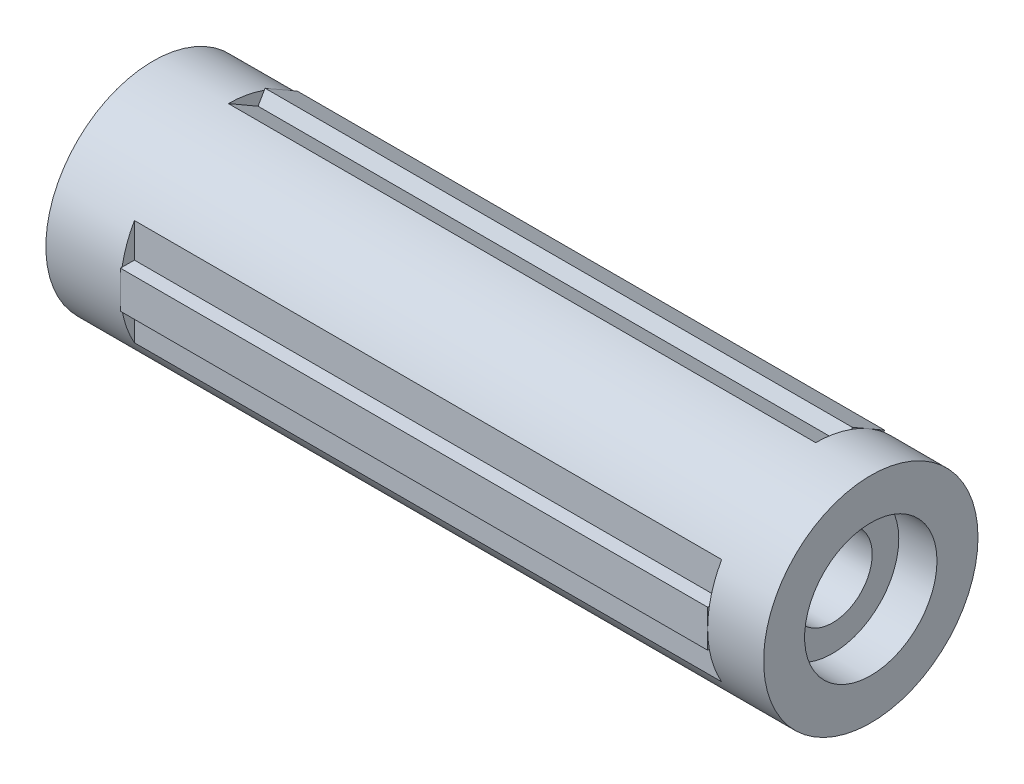
SolidWorks part; units mm, degrees
material "PVC hart"
ref_plane "Ebene vorne" through (0, 0, 0) normal (0, 0, 1) x (1, 0, 0)
ref_plane "Ebene oben" through (0, 0, 0) normal (0, 1, 0) x (1, 0, 0)
ref_plane "Ebene rechts" through (0, 0, 0) normal (1, 0, 0) x (0, 0, -1)
sketch "Skizze1" plane through (0, 0, 0) normal (1, 0, 0) x (0, 0, -1)
  circle A0 centre (0, 0) radius 11.5
  dimension "D1" = 23
extrude "Aufsatz-Linear austragen1" add sketch "Skizze1" along normal blind 77
sketch "Skizze2" plane through (77, 0, 0) normal (1, 0, 0) x (0, 0, -1)
  circle A0 centre (0, 0) radius 7.1
  dimension "D1" = 14.2
extrude "Schnitt-Linear austragen1" cut sketch "Skizze2" against normal blind 4.1
sketch "Skizze3" plane through (72.9, 0, 0) normal (1, 0, 0) x (0, 0, -1)
  circle A0 centre (0, 0) radius 4.25
  dimension "D1" = 8.5
extrude "Schnitt-Linear austragen2" cut sketch "Skizze3" against normal blind 11
sketch "Skizze4" plane through (0, 0, 0) normal (-1, 0, 0) x (0, 0, 1)
  circle A0 centre (0, 0) radius 9.6
  dimension "D1" = 19.2
extrude "Schnitt-Linear austragen3" cut sketch "Skizze4" against normal blind 12.75
sketch "Skizze7" plane through (77, 0, 0) normal (1, 0, 0) x (0, 0, -1)
  line L0 (0, 13.4409) -> (0, -14.2481) construction
  line L1 (-11.5, 7.5) -> (-10, 7.5)
  line L2 (-11.5, 7.5) -> (-11.5, -7.5)
  line L3 (-11.5, -7.5) -> (-10, -7.5)
  line L4 (-10, 7.5) -> (-10, -7.5)
  dimension "D1" = 1.5
  dimension "D2" = 15
  dimension "D3" = 10
extrude "Schnitt-Linear austragen4" cut sketch "Skizze7" against normal blind 63 from offset 6 offset against normal yes
sketch "Skizze8" plane through (0, 0, 10) normal (0, 0, 1) x (1, 0, 0)
  line L0 (71, -5.6789) -> (71, 5.6789) construction
  line L1 (8, 2) -> (71, 2)
  line L2 (8, 2) -> (8, -2)
  line L3 (8, -2) -> (71, -2)
  line L4 (71, 2) -> (71, -2)
  line L5 (8, 2) -> (71, -2) construction
  line L6 (8, -2) -> (71, 2) construction
  line L7 (12.65, 0) -> (-12.65, 0) construction
  point P0 (39.5, 0)
  dimension "D1" = 31.5
  dimension "D3" = 63
  dimension "D4" = 4
extrude "Aufsatz-Linear austragen2" add sketch "Skizze8" along normal blind 1.5
sketch "Skizze10" plane through (12.75, 0, 0) normal (-1, 0, 0) x (0, 0, 1)
  line L1 (4.0389, -2.2407) -> (3.96, 2.3774)
  line L2 (3.96, 2.3774) -> (-0.0789, 4.6181)
  line L3 (-0.0789, 4.6181) -> (-4.0389, 2.2407)
  line L4 (-4.0389, 2.2407) -> (-3.96, -2.3774)
  line L5 (-3.96, -2.3774) -> (0.0789, -4.6181)
  line L6 (0.0789, -4.6181) -> (4.0389, -2.2407)
  circle A0 centre (0, 0) radius 4 construction
  dimension "D1" = 8
extrude "Schnitt-Linear austragen6" cut sketch "Skizze10" against normal blind 13.5
sketch "Skizze12" plane through (26.25, 0, 0) normal (-1, 0, 0) x (0, 0, 1)
  circle A0 centre (0, 0) radius 3
  dimension "D1" = 6
extrude "Schnitt-Linear austragen7" cut sketch "Skizze12" against normal blind 2
pattern_circular "Kreismuster3" count 3 over 360 about axis through (77, 0, 0) along (-1, 0, 0) of "Aufsatz-Linear austragen2", "Schnitt-Linear austragen4"
